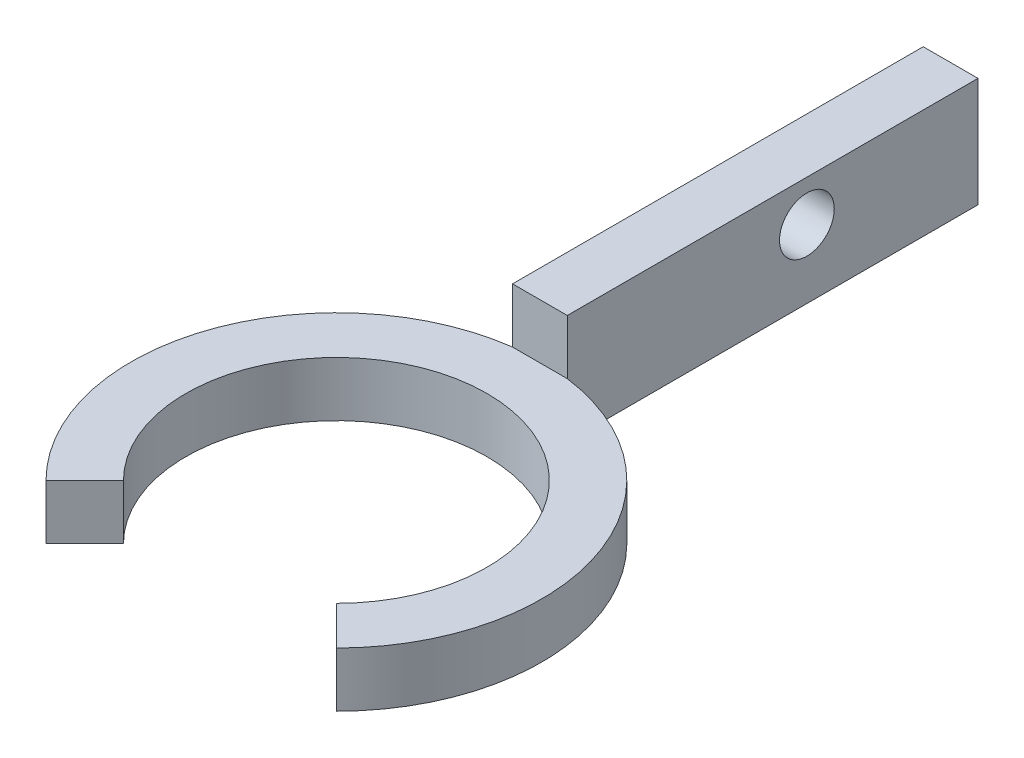
SolidWorks part; units mm, degrees
material "ABS"
ref_plane "Front Plane" through (0, 0, 0) normal (0, 0, 1) x (1, 0, 0)
ref_plane "Top Plane" through (0, 0, 0) normal (0, 1, 0) x (1, 0, 0)
ref_plane "Right Plane" through (0, 0, 0) normal (1, 0, 0) x (0, 0, -1)
sketch "Sketch1" plane through (0, 0, 0) normal (0, 1, 0) x (1, 0, 0)
  line L0 (3.8891, -3.8891) -> (5.3033, -5.3033)
  line L2 (-5.3033, -5.3033) -> (-3.8891, -3.8891)
  arc A0 (5.3033, -5.3033) -> (-5.3033, -5.3033) centre (0, 0) ccw
  arc A1 (3.8891, -3.8891) -> (-3.8891, -3.8891) centre (0, 0) ccw
  dimension "D1" = 15
  dimension "D2" = 11
extrude "Boss-Extrude1" add sketch "Sketch1" along normal blind 2
sketch "Sketch2" plane through (0, 2, 0) normal (0, 1, 0) x (1, 0, 0)
  line L1 (-1, 7.433) -> (1, 7.433)
  line L2 (-1, 7.433) -> (-1, 22.433)
  line L3 (-1, 22.433) -> (1, 22.433)
  line L4 (1, 7.433) -> (1, 22.433)
  arc A0 (5.3033, -5.3033) -> (-5.3033, -5.3033) centre (0, 0) ccw construction
  dimension "D1" = 2
  dimension "D2" = 1
  dimension "D3" = 15
extrude "Boss-Extrude2" add sketch "Sketch2" against normal blind 2 and the other way blind 2
sketch "Sketch3" plane through (1, 0, 0) normal (1, 0, 0) x (0, 0, -1)
  circle A0 centre (16.183, 2.5) radius 1
extrude "Cut-Extrude1" cut sketch "Sketch3" against normal through all
